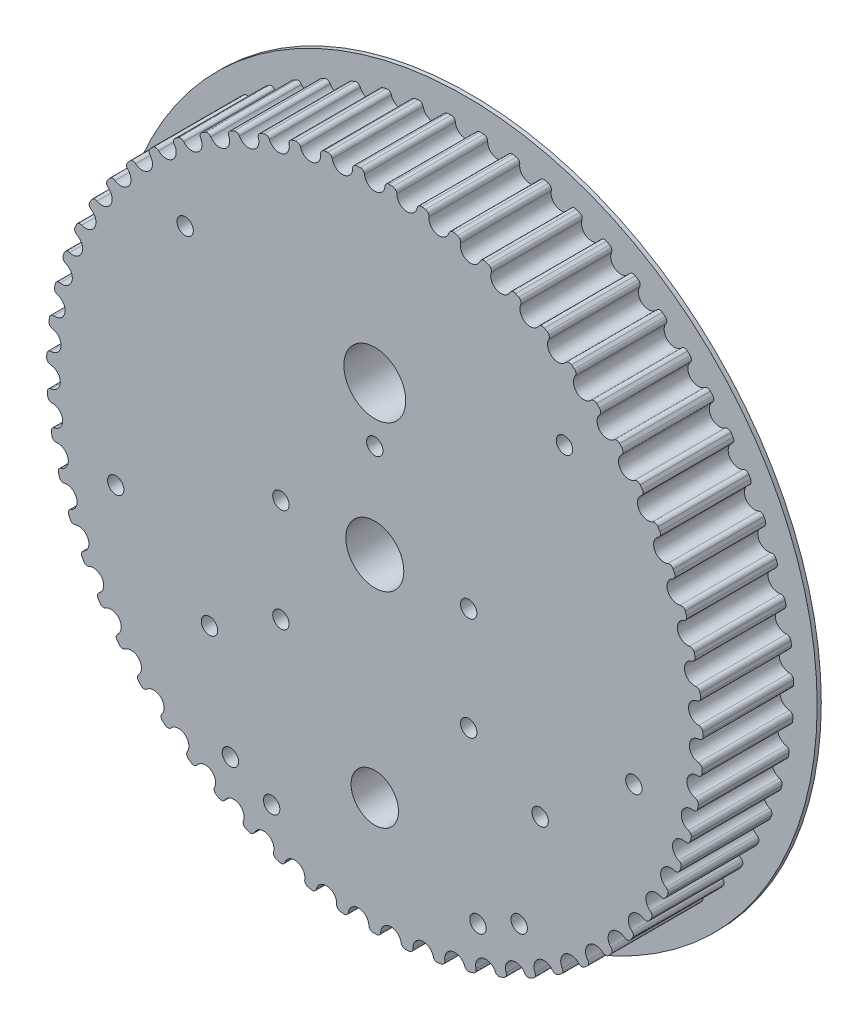
SolidWorks part; units mm, degrees
material "PETG"
ref_plane "Front Plane" through (0, 0, 0) normal (0, 0, 1) x (1, 0, 0)
ref_plane "Top Plane" through (0, 0, 0) normal (0, 1, 0) x (1, 0, 0)
ref_plane "Right Plane" through (0, 0, 0) normal (1, 0, 0) x (0, 0, -1)
sketch "Sketch1" plane through (0, 0, 0) normal (0, 0, 1) x (1, 0, 0)
  line L0 (0, 0) -> (0, 50000) construction
  line L1 (0, 0) -> (3.9983, 80.1144) construction
  line L2 (0, 0) -> (-3.9983, 80.1144) construction
  circle A0 centre (0, 0) radius 80.2141 construction
  arc A1 (-2.4816, 78.5352) -> (2.4816, 78.5352) centre (0, 78.74) ccw
  arc A2 (3.9642, 79.4311) -> (-3.9642, 79.4311) centre (0, 0) ccw construction
  arc A3 (-2.4816, 78.5352) -> (-3.5225, 79.452) centre (-3.4782, 78.4529) ccw
  arc A4 (3.5225, 79.452) -> (2.4816, 78.5352) centre (3.4782, 78.4529) ccw
  arc A5 (-3.5225, 79.452) -> (-3.9642, 79.4311) centre (0, 0) ccw
  arc A6 (3.5225, 79.452) -> (3.9642, 79.4311) centre (0, 0) cw
  arc A7 (4.4059, 79.4079) -> (3.9642, 79.4311) centre (0, 0) ccw
  arc A8 (5.3503, 78.392) -> (4.4059, 79.4079) centre (4.3505, 78.4094) ccw
  arc A9 (5.3503, 78.392) -> (10.2888, 77.8978) centre (7.84, 78.3487) ccw
  arc A10 (11.4158, 78.7064) -> (10.2888, 77.8978) centre (11.2723, 77.7168) ccw
  arc A11 (11.4158, 78.7064) -> (11.8533, 78.6417) centre (0, 0) cw
  arc A12 (12.2905, 78.5746) -> (11.8533, 78.6417) centre (0, 0) ccw
  arc A13 (13.1291, 77.4697) -> (12.2905, 78.5746) centre (12.1359, 77.5866) ccw
  arc A14 (13.1291, 77.4697) -> (17.9938, 76.4863) centre (15.602, 77.1788) ccw
  arc A15 (19.1957, 77.1787) -> (17.9938, 76.4863) centre (18.9544, 76.2082) ccw
  arc A16 (19.1957, 77.1787) -> (19.6246, 77.0707) centre (0, 0) cw
  arc A17 (20.0529, 76.9604) -> (19.6246, 77.0707) centre (0, 0) ccw
  arc A18 (20.7773, 75.7775) -> (20.0529, 76.9604) centre (19.8008, 75.9927) ccw
  arc A19 (20.7773, 75.7775) -> (25.52, 74.3146) centre (23.209, 75.2418) ccw
  arc A20 (26.7848, 74.8839) -> (25.52, 74.3146) centre (26.4481, 73.9423) ccw
  arc A21 (26.7848, 74.8839) -> (27.2009, 74.7338) centre (0, 0) cw
  arc A22 (27.616, 74.5813) -> (27.2009, 74.7338) centre (0, 0) ccw
  arc A23 (28.2191, 73.3322) -> (27.616, 74.5813) centre (27.2688, 73.6436) ccw
  arc A24 (28.2191, 73.3322) -> (32.7925, 71.4044) centre (30.5854, 72.557) ccw
  arc A25 (34.1078, 71.8448) -> (32.7925, 71.4044) centre (33.6789, 70.9415) ccw
  arc A26 (34.1078, 71.8448) -> (34.5068, 71.6541) centre (0, 0) cw
  arc A27 (34.9047, 71.4611) -> (34.5068, 71.6541) centre (0, 0) ccw
  arc A28 (35.3804, 70.1581) -> (34.9047, 71.4611) centre (34.4658, 70.5625) ccw
  arc A29 (35.3804, 70.1581) -> (39.7391, 67.7845) centre (37.6577, 69.1512) ccw
  arc A30 (41.0917, 68.0918) -> (39.7391, 67.7845) centre (40.575, 67.2356) ccw
  arc A31 (41.0917, 68.0918) -> (41.4697, 67.8622) centre (0, 0) cw
  arc A32 (41.8465, 67.6306) -> (41.4697, 67.8622) centre (0, 0) ccw
  arc A33 (42.1901, 66.2867) -> (41.8465, 67.6306) centre (41.3203, 66.7802) ccw
  arc A34 (42.1901, 66.2867) -> (46.2908, 63.4909) centre (44.3558, 65.058) ccw
  arc A35 (47.6673, 63.662) -> (46.2908, 63.4909) centre (47.0679, 62.8615) ccw
  arc A36 (47.6673, 63.662) -> (48.0206, 63.3959) centre (0, 0) cw
  arc A37 (48.3724, 63.1279) -> (48.0206, 63.3959) centre (0, 0) ccw
  arc A38 (48.5805, 61.7566) -> (48.3724, 63.1279) centre (47.7641, 62.3342) ccw
  arc A39 (48.5805, 61.7566) -> (52.3824, 58.5663) centre (50.6131, 60.3183) ccw
  arc A40 (53.7691, 58.5995) -> (52.3824, 58.5663) centre (53.093, 57.8627) ccw
  arc A41 (53.7691, 58.5995) -> (54.0941, 58.2996) centre (0, 0) cw
  arc A42 (54.4175, 57.9979) -> (54.0941, 58.2996) centre (0, 0) ccw
  arc A43 (54.488, 56.6126) -> (54.4175, 57.9979) centre (53.7333, 57.2686) ccw
  arc A44 (54.488, 56.6126) -> (57.9535, 53.0597) centre (56.3674, 54.9792) ccw
  arc A45 (59.3365, 52.9547) -> (57.9535, 53.0597) centre (58.5904, 52.2888) ccw
  arc A46 (59.3365, 52.9547) -> (59.6301, 52.6239) centre (0, 0) cw
  arc A47 (59.9218, 52.2915) -> (59.6301, 52.6239) centre (0, 0) ccw
  arc A48 (59.8541, 50.9061) -> (59.9218, 52.2915) centre (59.1684, 51.634) ccw
  arc A49 (59.8541, 50.9061) -> (62.9485, 47.0257) centre (61.5614, 49.0936) ccw
  arc A50 (64.3143, 46.7835) -> (62.9485, 47.0257) centre (63.5056, 46.1953) ccw
  arc A51 (64.3143, 46.7835) -> (64.5734, 46.4251) centre (0, 0) cw
  arc A52 (64.8306, 46.0653) -> (64.5734, 46.4251) centre (0, 0) ccw
  arc A53 (64.6252, 44.6936) -> (64.8306, 46.0653) centre (64.0154, 45.4861) ccw
  arc A54 (64.6252, 44.6936) -> (67.318, 40.5244) centre (66.1436, 42.7201) ccw
  arc A55 (68.6528, 40.1474) -> (67.318, 40.5244) centre (67.7896, 39.6426) ccw
  arc A56 (68.6528, 40.1474) -> (68.875, 39.765) centre (0, 0) cw
  arc A57 (69.0951, 39.3814) -> (68.875, 39.765) centre (0, 0) ccw
  arc A58 (68.7541, 38.0369) -> (69.0951, 39.3814) centre (68.2263, 38.8862) ccw
  arc A59 (68.7541, 38.0369) -> (71.0184, 33.6203) centre (70.0685, 35.922) ccw
  arc A60 (72.309, 33.1123) -> (71.0184, 33.6203) centre (71.3998, 32.6959) ccw
  arc A61 (72.309, 33.1123) -> (72.4921, 32.7097) centre (0, 0) cw
  arc A62 (72.6728, 32.306) -> (72.4921, 32.7097) centre (0, 0) ccw
  arc A63 (72.1997, 31.0021) -> (72.6728, 32.306) centre (71.7591, 31.8998) ccw
  arc A64 (72.1997, 31.0021) -> (74.013, 26.3821) centre (73.297, 28.767) ccw
  arc A65 (75.2466, 25.7481) -> (74.013, 26.3821) centre (74.3005, 25.4243) ccw
  arc A66 (75.2466, 25.7481) -> (75.3887, 25.3292) centre (0, 0) cw
  arc A67 (75.5284, 24.9096) -> (75.3887, 25.3292) centre (0, 0) ccw
  arc A68 (74.9278, 23.6593) -> (75.5284, 24.9096) centre (74.5787, 24.5964) ccw
  arc A69 (74.9278, 23.6593) -> (76.272, 18.8817) centre (75.797, 21.326) ccw
  arc A70 (77.4364, 18.128) -> (76.272, 18.8817) centre (76.4627, 17.9001) ccw
  arc A71 (77.4364, 18.128) -> (77.536, 17.6971) centre (0, 0) cw
  arc A72 (77.6332, 17.2656) -> (77.536, 17.6971) centre (0, 0) ccw
  arc A73 (76.9111, 16.0814) -> (77.6332, 17.2656) centre (76.6571, 17.0485) ccw
  arc A74 (76.9111, 16.0814) -> (77.773, 11.1936) centre (77.5438, 13.6731) ccw
  arc A75 (78.8566, 10.3277) -> (77.773, 11.1936) centre (77.865, 10.1979) ccw
  arc A76 (78.8566, 10.3277) -> (78.9128, 9.8891) centre (0, 0) cw
  arc A77 (78.9666, 9.4501) -> (78.9128, 9.8891) centre (0, 0) ccw
  arc A78 (78.1301, 8.3436) -> (78.9666, 9.4501) centre (77.9736, 9.3312) ccw
  arc A79 (78.1301, 8.3436) -> (78.501, 3.3943) centre (78.5198, 5.8842) ccw
  arc A80 (79.493, 2.4248) -> (78.501, 3.3943) centre (78.4935, 2.3943) ccw
  arc A81 (79.493, 2.4248) -> (79.5053, 1.9827) centre (0, 0) cw
  arc A82 (79.5151, 1.5406) -> (79.5053, 1.9827) centre (0, 0) ccw
  arc A83 (78.5726, 0.5229) -> (79.5151, 1.5406) centre (78.5153, 1.5212) ccw
  arc A84 (78.5726, 0.5229) -> (78.4489, -4.4387) centre (78.7155, -1.963) ccw
  arc A85 (79.3394, -5.5022) -> (78.4489, -4.4387) centre (78.3418, -5.433) ccw
  arc A86 (79.3394, -5.5022) -> (79.3076, -5.9433) centre (0, 0) cw
  arc A87 (79.2733, -6.3842) -> (79.3076, -5.9433) centre (0, 0) ccw
  arc A88 (78.2343, -7.3031) -> (79.2733, -6.3842) centre (78.2766, -6.3039) ccw
  arc A89 (78.2343, -7.3031) -> (77.6171, -12.2277) centre (78.1289, -9.7908) ccw
  arc A90 (78.3973, -13.3745) -> (77.6171, -12.2277) centre (77.4116, -13.2063) ccw
  arc A91 (78.3973, -13.3745) -> (78.3218, -13.8102) centre (0, 0) cw
  arc A92 (78.2438, -14.2456) -> (78.3218, -13.8102) centre (0, 0) ccw
  arc A93 (77.1183, -15.0564) -> (78.2438, -14.2456) centre (77.2599, -14.0665) ccw
  arc A94 (77.1183, -15.0564) -> (76.0139, -19.8951) centre (76.7658, -17.5213) ccw
  arc A95 (76.6761, -21.1139) -> (76.0139, -19.8951) centre (75.712, -20.8484) ccw
  arc A96 (76.6761, -21.1139) -> (76.5575, -21.5399) centre (0, 0) cw
  arc A97 (76.4365, -21.9653) -> (76.5575, -21.5399) centre (0, 0) ccw
  arc A98 (75.236, -22.6601) -> (76.4365, -21.9653) centre (75.4754, -21.6892) ccw
  arc A99 (75.236, -22.6601) -> (73.6553, -27.3648) centre (74.6398, -25.0776) ccw
  arc A100 (74.1928, -28.6434) -> (73.6553, -27.3648) centre (73.2599, -28.2833) ccw
  arc A101 (74.1928, -28.6434) -> (74.0324, -29.0556) centre (0, 0) cw
  arc A102 (73.8697, -29.4668) -> (74.0324, -29.0556) centre (0, 0) ccw
  arc A103 (72.6059, -30.0386) -> (73.8697, -29.4668) centre (72.9408, -29.0963) ccw
  arc A104 (72.6059, -30.0386) -> (70.5647, -34.5625) centre (71.772, -32.3847) ccw
  arc A105 (70.9722, -35.8883) -> (70.5647, -34.5625) centre (70.0798, -35.4371) ccw
  arc A106 (70.9722, -35.8883) -> (70.7715, -36.2824) centre (0, 0) cw
  arc A107 (70.5686, -36.6754) -> (70.7715, -36.2824) centre (0, 0) ccw
  arc A108 (69.2543, -37.1185) -> (70.5686, -36.6754) centre (69.6813, -36.2143) ccw
  arc A109 (69.2543, -37.1185) -> (66.7727, -41.4167) centre (68.1908, -39.37) ccw
  arc A110 (67.0462, -42.7765) -> (66.7727, -41.4167) centre (66.2031, -42.2387) ccw
  arc A111 (67.0462, -42.7765) -> (66.8073, -43.1487) centre (0, 0) cw
  arc A112 (66.5663, -43.5196) -> (66.8073, -43.1487) centre (0, 0) ccw
  arc A113 (65.2143, -43.8295) -> (66.5663, -43.5196) centre (65.7293, -42.9723) ccw
  arc A114 (65.2143, -43.8295) -> (62.3171, -47.8593) centre (63.932, -45.964) ccw
  arc A115 (62.4538, -49.2396) -> (62.3171, -47.8593) centre (61.6686, -48.6205) ccw
  arc A116 (62.4538, -49.2396) -> (62.1791, -49.5861) centre (0, 0) cw
  arc A117 (61.9023, -49.9312) -> (62.1791, -49.5861) centre (0, 0) ccw
  arc A118 (60.5262, -50.105) -> (61.9023, -49.9312) centre (61.124, -49.3033) ccw
  arc A119 (60.5262, -50.105) -> (57.2422, -53.8263) centre (59.0378, -52.1011) ccw
  arc A120 (57.2408, -55.2133) -> (57.2422, -53.8263) centre (56.5211, -54.5191) ccw
  arc A121 (57.2408, -55.2133) -> (56.9329, -55.5308) centre (0, 0) cw
  arc A122 (56.6232, -55.8465) -> (56.9329, -55.5308) centre (0, 0) ccw
  arc A123 (55.2366, -55.8825) -> (56.6232, -55.8465) centre (55.9112, -55.1443) ccw
  arc A124 (55.2366, -55.8825) -> (51.5984, -59.2583) centre (53.5568, -57.7205) ccw
  arc A125 (51.4589, -60.6383) -> (51.5984, -59.2583) centre (50.8119, -59.8758) ccw
  arc A126 (51.4589, -60.6383) -> (51.1209, -60.9235) centre (0, 0) cw
  arc A127 (50.7813, -61.2069) -> (51.1209, -60.9235) centre (0, 0) ccw
  arc A128 (49.398, -61.1046) -> (50.7813, -61.2069) centre (50.1428, -60.4372) ccw
  arc A129 (49.398, -61.1046) -> (45.4418, -64.1013) centre (47.5436, -62.7662) ccw
  arc A130 (45.1656, -65.4606) -> (45.4418, -64.1013) centre (44.5977, -64.6375) ccw
  arc A131 (45.1656, -65.4606) -> (44.8008, -65.7108) centre (0, 0) cw
  arc A132 (44.4347, -65.9589) -> (44.8008, -65.7108) centre (0, 0) ccw
  arc A133 (43.0685, -65.7194) -> (44.4347, -65.9589) centre (43.876, -65.1295) ccw
  arc A134 (43.0685, -65.7194) -> (38.8335, -68.3073) centre (41.0578, -67.1881) ccw
  arc A135 (38.4234, -69.6324) -> (38.8335, -68.3073) centre (37.9402, -68.7568) ccw
  arc A136 (38.4234, -69.6324) -> (38.0355, -69.845) centre (0, 0) cw
  arc A137 (37.6465, -70.0554) -> (38.0355, -69.845) centre (0, 0) ccw
  arc A138 (36.311, -69.6811) -> (37.6465, -70.0554) centre (37.1732, -69.1745) ccw
  arc A139 (36.311, -69.6811) -> (31.8393, -71.8345) centre (34.164, -70.9423) ccw
  arc A140 (31.2993, -73.1121) -> (31.8393, -71.8345) centre (30.9057, -72.1928) ccw
  arc A141 (31.2993, -73.1121) -> (30.8922, -73.285) centre (0, 0) cw
  arc A142 (30.4842, -73.4557) -> (30.8922, -73.285) centre (0, 0) ccw
  arc A143 (29.1925, -72.9502) -> (30.4842, -73.4557) centre (30.1009, -72.532) ccw
  arc A144 (29.1925, -72.9502) -> (24.5287, -74.6477) centre (26.9307, -73.9914) ccw
  arc A145 (23.8641, -75.8652) -> (24.5287, -74.6477) centre (23.5641, -74.9113) ccw
  arc A146 (23.8641, -75.8652) -> (23.4419, -75.9967) centre (0, 0) cw
  arc A147 (23.0189, -76.1259) -> (23.4419, -75.9967) centre (0, 0) ccw
  arc A148 (21.784, -75.4943) -> (23.0189, -76.1259) centre (22.7295, -75.1687) ccw
  arc A149 (21.784, -75.4943) -> (16.9743, -76.719) centre (19.4297, -76.3051) ccw
  arc A150 (16.1918, -77.8643) -> (16.9743, -76.719) centre (15.9882, -76.8852) ccw
  arc A151 (16.1918, -77.8643) -> (15.7586, -77.9531) centre (0, 0) cw
  arc A152 (15.3248, -78.0395) -> (15.7586, -77.9531) centre (0, 0) ccw
  arc A153 (14.1589, -77.2882) -> (15.3248, -78.0395) centre (15.1321, -77.0583) ccw
  arc A154 (14.1589, -77.2882) -> (9.2512, -78.0279) centre (11.7356, -77.8605) ccw
  arc A155 (8.3586, -79.0895) -> (9.2512, -78.0279) centre (8.2535, -78.0951) ccw
  arc A156 (8.3586, -79.0895) -> (7.9186, -79.1348) centre (0, 0) cw
  arc A157 (7.4784, -79.1776) -> (7.9186, -79.1348) centre (0, 0) ccw
  arc A158 (6.3931, -78.3139) -> (7.4784, -79.1776) centre (7.3844, -78.182) ccw
  arc A159 (6.3931, -78.3139) -> (1.4362, -78.5613) centre (3.9249, -78.6421) ccw
  arc A160 (0.4423, -79.5288) -> (1.4362, -78.5613) centre (0.4367, -78.5288) ccw
  arc A161 (0.4423, -79.5288) -> (0, -79.53) centre (0, 0) cw
  arc A162 (-0.4423, -79.5288) -> (0, -79.53) centre (0, 0) ccw
  arc A163 (-1.4362, -78.5613) -> (-0.4423, -79.5288) centre (-0.4367, -78.5288) ccw
  arc A164 (-1.4362, -78.5613) -> (-6.3931, -78.3139) centre (-3.9249, -78.6421) ccw
  arc A165 (-7.4784, -79.1776) -> (-6.3931, -78.3139) centre (-7.3844, -78.182) ccw
  arc A166 (-7.4784, -79.1776) -> (-7.9186, -79.1348) centre (0, 0) cw
  arc A167 (-8.3586, -79.0895) -> (-7.9186, -79.1348) centre (0, 0) ccw
  arc A168 (-9.2512, -78.0279) -> (-8.3586, -79.0895) centre (-8.2535, -78.0951) ccw
  arc A169 (-9.2512, -78.0279) -> (-14.1589, -77.2882) centre (-11.7356, -77.8605) ccw
  arc A170 (-15.3248, -78.0395) -> (-14.1589, -77.2882) centre (-15.1321, -77.0583) ccw
  arc A171 (-15.3248, -78.0395) -> (-15.7586, -77.9531) centre (0, 0) cw
  arc A172 (-16.1918, -77.8643) -> (-15.7586, -77.9531) centre (0, 0) ccw
  arc A173 (-16.9743, -76.719) -> (-16.1918, -77.8643) centre (-15.9882, -76.8852) ccw
  arc A174 (-16.9743, -76.719) -> (-21.784, -75.4943) centre (-19.4297, -76.3051) ccw
  arc A175 (-23.0189, -76.1259) -> (-21.784, -75.4943) centre (-22.7295, -75.1687) ccw
  arc A176 (-23.0189, -76.1259) -> (-23.4419, -75.9967) centre (0, 0) cw
  arc A177 (-23.8641, -75.8652) -> (-23.4419, -75.9967) centre (0, 0) ccw
  arc A178 (-24.5287, -74.6477) -> (-23.8641, -75.8652) centre (-23.5641, -74.9113) ccw
  arc A179 (-24.5287, -74.6477) -> (-29.1925, -72.9502) centre (-26.9307, -73.9914) ccw
  arc A180 (-30.4842, -73.4557) -> (-29.1925, -72.9502) centre (-30.1009, -72.532) ccw
  arc A181 (-30.4842, -73.4557) -> (-30.8922, -73.285) centre (0, 0) cw
  arc A182 (-31.2993, -73.1121) -> (-30.8922, -73.285) centre (0, 0) ccw
  arc A183 (-31.8393, -71.8345) -> (-31.2993, -73.1121) centre (-30.9057, -72.1928) ccw
  arc A184 (-31.8393, -71.8345) -> (-36.311, -69.6811) centre (-34.164, -70.9423) ccw
  arc A185 (-37.6465, -70.0554) -> (-36.311, -69.6811) centre (-37.1732, -69.1745) ccw
  arc A186 (-37.6465, -70.0554) -> (-38.0355, -69.845) centre (0, 0) cw
  arc A187 (-38.4234, -69.6324) -> (-38.0355, -69.845) centre (0, 0) ccw
  arc A188 (-38.8335, -68.3073) -> (-38.4234, -69.6324) centre (-37.9402, -68.7568) ccw
  arc A189 (-38.8335, -68.3073) -> (-43.0685, -65.7194) centre (-41.0578, -67.1881) ccw
  arc A190 (-44.4347, -65.9589) -> (-43.0685, -65.7194) centre (-43.876, -65.1295) ccw
  arc A191 (-44.4347, -65.9589) -> (-44.8008, -65.7108) centre (0, 0) cw
  arc A192 (-45.1656, -65.4606) -> (-44.8008, -65.7108) centre (0, 0) ccw
  arc A193 (-45.4418, -64.1013) -> (-45.1656, -65.4606) centre (-44.5977, -64.6375) ccw
  arc A194 (-45.4418, -64.1013) -> (-49.398, -61.1046) centre (-47.5436, -62.7662) ccw
  arc A195 (-50.7813, -61.2069) -> (-49.398, -61.1046) centre (-50.1428, -60.4372) ccw
  arc A196 (-50.7813, -61.2069) -> (-51.1209, -60.9235) centre (0, 0) cw
  arc A197 (-51.4589, -60.6383) -> (-51.1209, -60.9235) centre (0, 0) ccw
  arc A198 (-51.5984, -59.2583) -> (-51.4589, -60.6383) centre (-50.8119, -59.8758) ccw
  arc A199 (-51.5984, -59.2583) -> (-55.2366, -55.8825) centre (-53.5568, -57.7205) ccw
  arc A200 (-56.6232, -55.8465) -> (-55.2366, -55.8825) centre (-55.9112, -55.1443) ccw
  arc A201 (-56.6232, -55.8465) -> (-56.9329, -55.5308) centre (0, 0) cw
  arc A202 (-57.2408, -55.2133) -> (-56.9329, -55.5308) centre (0, 0) ccw
  arc A203 (-57.2422, -53.8263) -> (-57.2408, -55.2133) centre (-56.5211, -54.5191) ccw
  arc A204 (-57.2422, -53.8263) -> (-60.5262, -50.105) centre (-59.0378, -52.1011) ccw
  arc A205 (-61.9023, -49.9312) -> (-60.5262, -50.105) centre (-61.124, -49.3033) ccw
  arc A206 (-61.9023, -49.9312) -> (-62.1791, -49.5861) centre (0, 0) cw
  arc A207 (-62.4538, -49.2396) -> (-62.1791, -49.5861) centre (0, 0) ccw
  arc A208 (-62.3171, -47.8593) -> (-62.4538, -49.2396) centre (-61.6686, -48.6205) ccw
  arc A209 (-62.3171, -47.8593) -> (-65.2143, -43.8295) centre (-63.932, -45.964) ccw
  arc A210 (-66.5663, -43.5196) -> (-65.2143, -43.8295) centre (-65.7293, -42.9723) ccw
  arc A211 (-66.5663, -43.5196) -> (-66.8073, -43.1487) centre (0, 0) cw
  arc A212 (-67.0462, -42.7765) -> (-66.8073, -43.1487) centre (0, 0) ccw
  arc A213 (-66.7727, -41.4167) -> (-67.0462, -42.7765) centre (-66.2031, -42.2387) ccw
  arc A214 (-66.7727, -41.4167) -> (-69.2543, -37.1185) centre (-68.1908, -39.37) ccw
  arc A215 (-70.5686, -36.6754) -> (-69.2543, -37.1185) centre (-69.6813, -36.2143) ccw
  arc A216 (-70.5686, -36.6754) -> (-70.7715, -36.2824) centre (0, 0) cw
  arc A217 (-70.9722, -35.8883) -> (-70.7715, -36.2824) centre (0, 0) ccw
  arc A218 (-70.5647, -34.5625) -> (-70.9722, -35.8883) centre (-70.0798, -35.4371) ccw
  arc A219 (-70.5647, -34.5625) -> (-72.6059, -30.0386) centre (-71.772, -32.3847) ccw
  arc A220 (-73.8697, -29.4668) -> (-72.6059, -30.0386) centre (-72.9408, -29.0963) ccw
  arc A221 (-73.8697, -29.4668) -> (-74.0324, -29.0556) centre (0, 0) cw
  arc A222 (-74.1928, -28.6434) -> (-74.0324, -29.0556) centre (0, 0) ccw
  arc A223 (-73.6553, -27.3648) -> (-74.1928, -28.6434) centre (-73.2599, -28.2833) ccw
  arc A224 (-73.6553, -27.3648) -> (-75.236, -22.6601) centre (-74.6398, -25.0776) ccw
  arc A225 (-76.4365, -21.9653) -> (-75.236, -22.6601) centre (-75.4754, -21.6892) ccw
  arc A226 (-76.4365, -21.9653) -> (-76.5575, -21.5399) centre (0, 0) cw
  arc A227 (-76.6761, -21.1139) -> (-76.5575, -21.5399) centre (0, 0) ccw
  arc A228 (-76.0139, -19.8951) -> (-76.6761, -21.1139) centre (-75.712, -20.8484) ccw
  arc A229 (-76.0139, -19.8951) -> (-77.1183, -15.0564) centre (-76.7658, -17.5213) ccw
  arc A230 (-78.2438, -14.2456) -> (-77.1183, -15.0564) centre (-77.2599, -14.0665) ccw
  arc A231 (-78.2438, -14.2456) -> (-78.3218, -13.8102) centre (0, 0) cw
  arc A232 (-78.3973, -13.3745) -> (-78.3218, -13.8102) centre (0, 0) ccw
  arc A233 (-77.6171, -12.2277) -> (-78.3973, -13.3745) centre (-77.4116, -13.2063) ccw
  arc A234 (-77.6171, -12.2277) -> (-78.2343, -7.3031) centre (-78.1289, -9.7908) ccw
  arc A235 (-79.2733, -6.3842) -> (-78.2343, -7.3031) centre (-78.2766, -6.3039) ccw
  arc A236 (-79.2733, -6.3842) -> (-79.3076, -5.9433) centre (0, 0) cw
  arc A237 (-79.3394, -5.5022) -> (-79.3076, -5.9433) centre (0, 0) ccw
  arc A238 (-78.4489, -4.4387) -> (-79.3394, -5.5022) centre (-78.3418, -5.433) ccw
  arc A239 (-78.4489, -4.4387) -> (-78.5726, 0.5229) centre (-78.7155, -1.963) ccw
  arc A240 (-79.5151, 1.5406) -> (-78.5726, 0.5229) centre (-78.5153, 1.5212) ccw
  arc A241 (-79.5151, 1.5406) -> (-79.5053, 1.9827) centre (0, 0) cw
  arc A242 (-79.493, 2.4248) -> (-79.5053, 1.9827) centre (0, 0) ccw
  arc A243 (-78.501, 3.3943) -> (-79.493, 2.4248) centre (-78.4935, 2.3943) ccw
  arc A244 (-78.501, 3.3943) -> (-78.1301, 8.3436) centre (-78.5198, 5.8842) ccw
  arc A245 (-78.9666, 9.4501) -> (-78.1301, 8.3436) centre (-77.9736, 9.3312) ccw
  arc A246 (-78.9666, 9.4501) -> (-78.9128, 9.8891) centre (0, 0) cw
  arc A247 (-78.8566, 10.3277) -> (-78.9128, 9.8891) centre (0, 0) ccw
  arc A248 (-77.773, 11.1936) -> (-78.8566, 10.3277) centre (-77.865, 10.1979) ccw
  arc A249 (-77.773, 11.1936) -> (-76.9111, 16.0814) centre (-77.5438, 13.6731) ccw
  arc A250 (-77.6332, 17.2656) -> (-76.9111, 16.0814) centre (-76.6571, 17.0485) ccw
  arc A251 (-77.6332, 17.2656) -> (-77.536, 17.6971) centre (0, 0) cw
  arc A252 (-77.4364, 18.128) -> (-77.536, 17.6971) centre (0, 0) ccw
  arc A253 (-76.272, 18.8817) -> (-77.4364, 18.128) centre (-76.4627, 17.9001) ccw
  arc A254 (-76.272, 18.8817) -> (-74.9278, 23.6593) centre (-75.797, 21.326) ccw
  arc A255 (-75.5284, 24.9096) -> (-74.9278, 23.6593) centre (-74.5787, 24.5964) ccw
  arc A256 (-75.5284, 24.9096) -> (-75.3887, 25.3292) centre (0, 0) cw
  arc A257 (-75.2466, 25.7481) -> (-75.3887, 25.3292) centre (0, 0) ccw
  arc A258 (-74.013, 26.3821) -> (-75.2466, 25.7481) centre (-74.3005, 25.4243) ccw
  arc A259 (-74.013, 26.3821) -> (-72.1997, 31.0021) centre (-73.297, 28.767) ccw
  arc A260 (-72.6728, 32.306) -> (-72.1997, 31.0021) centre (-71.7591, 31.8998) ccw
  arc A261 (-72.6728, 32.306) -> (-72.4921, 32.7097) centre (0, 0) cw
  arc A262 (-72.309, 33.1123) -> (-72.4921, 32.7097) centre (0, 0) ccw
  arc A263 (-71.0184, 33.6203) -> (-72.309, 33.1123) centre (-71.3998, 32.6959) ccw
  arc A264 (-71.0184, 33.6203) -> (-68.7541, 38.0369) centre (-70.0685, 35.922) ccw
  arc A265 (-69.0951, 39.3814) -> (-68.7541, 38.0369) centre (-68.2263, 38.8862) ccw
  arc A266 (-69.0951, 39.3814) -> (-68.875, 39.765) centre (0, 0) cw
  arc A267 (-68.6528, 40.1474) -> (-68.875, 39.765) centre (0, 0) ccw
  arc A268 (-67.318, 40.5244) -> (-68.6528, 40.1474) centre (-67.7896, 39.6426) ccw
  arc A269 (-67.318, 40.5244) -> (-64.6252, 44.6936) centre (-66.1436, 42.7201) ccw
  arc A270 (-64.8306, 46.0653) -> (-64.6252, 44.6936) centre (-64.0154, 45.4861) ccw
  arc A271 (-64.8306, 46.0653) -> (-64.5734, 46.4251) centre (0, 0) cw
  arc A272 (-64.3143, 46.7835) -> (-64.5734, 46.4251) centre (0, 0) ccw
  arc A273 (-62.9485, 47.0257) -> (-64.3143, 46.7835) centre (-63.5056, 46.1953) ccw
  arc A274 (-62.9485, 47.0257) -> (-59.8541, 50.9061) centre (-61.5614, 49.0936) ccw
  arc A275 (-59.9218, 52.2915) -> (-59.8541, 50.9061) centre (-59.1684, 51.634) ccw
  arc A276 (-59.9218, 52.2915) -> (-59.6301, 52.6239) centre (0, 0) cw
  arc A277 (-59.3365, 52.9547) -> (-59.6301, 52.6239) centre (0, 0) ccw
  arc A278 (-57.9535, 53.0597) -> (-59.3365, 52.9547) centre (-58.5904, 52.2888) ccw
  arc A279 (-57.9535, 53.0597) -> (-54.488, 56.6126) centre (-56.3674, 54.9792) ccw
  arc A280 (-54.4175, 57.9979) -> (-54.488, 56.6126) centre (-53.7333, 57.2686) ccw
  arc A281 (-54.4175, 57.9979) -> (-54.0941, 58.2996) centre (0, 0) cw
  arc A282 (-53.7691, 58.5995) -> (-54.0941, 58.2996) centre (0, 0) ccw
  arc A283 (-52.3824, 58.5663) -> (-53.7691, 58.5995) centre (-53.093, 57.8627) ccw
  arc A284 (-52.3824, 58.5663) -> (-48.5805, 61.7566) centre (-50.6131, 60.3183) ccw
  arc A285 (-48.3724, 63.1279) -> (-48.5805, 61.7566) centre (-47.7641, 62.3342) ccw
  arc A286 (-48.3724, 63.1279) -> (-48.0206, 63.3959) centre (0, 0) cw
  arc A287 (-47.6673, 63.662) -> (-48.0206, 63.3959) centre (0, 0) ccw
  arc A288 (-46.2908, 63.4909) -> (-47.6673, 63.662) centre (-47.0679, 62.8615) ccw
  arc A289 (-46.2908, 63.4909) -> (-42.1901, 66.2867) centre (-44.3558, 65.058) ccw
  arc A290 (-41.8465, 67.6306) -> (-42.1901, 66.2867) centre (-41.3203, 66.7802) ccw
  arc A291 (-41.8465, 67.6306) -> (-41.4697, 67.8622) centre (0, 0) cw
  arc A292 (-41.0917, 68.0918) -> (-41.4697, 67.8622) centre (0, 0) ccw
  arc A293 (-39.7391, 67.7845) -> (-41.0917, 68.0918) centre (-40.575, 67.2356) ccw
  arc A294 (-39.7391, 67.7845) -> (-35.3804, 70.1581) centre (-37.6577, 69.1512) ccw
  arc A295 (-34.9047, 71.4611) -> (-35.3804, 70.1581) centre (-34.4658, 70.5625) ccw
  arc A296 (-34.9047, 71.4611) -> (-34.5068, 71.6541) centre (0, 0) cw
  arc A297 (-34.1078, 71.8448) -> (-34.5068, 71.6541) centre (0, 0) ccw
  arc A298 (-32.7925, 71.4044) -> (-34.1078, 71.8448) centre (-33.6789, 70.9415) ccw
  arc A299 (-32.7925, 71.4044) -> (-28.2191, 73.3322) centre (-30.5854, 72.557) ccw
  arc A300 (-27.616, 74.5813) -> (-28.2191, 73.3322) centre (-27.2688, 73.6436) ccw
  arc A301 (-27.616, 74.5813) -> (-27.2009, 74.7338) centre (0, 0) cw
  arc A302 (-26.7848, 74.8839) -> (-27.2009, 74.7338) centre (0, 0) ccw
  arc A303 (-25.52, 74.3146) -> (-26.7848, 74.8839) centre (-26.4481, 73.9423) ccw
  arc A304 (-25.52, 74.3146) -> (-20.7773, 75.7775) centre (-23.209, 75.2418) ccw
  arc A305 (-20.0529, 76.9604) -> (-20.7773, 75.7775) centre (-19.8008, 75.9927) ccw
  arc A306 (-20.0529, 76.9604) -> (-19.6246, 77.0707) centre (0, 0) cw
  arc A307 (-19.1957, 77.1787) -> (-19.6246, 77.0707) centre (0, 0) ccw
  arc A308 (-17.9938, 76.4863) -> (-19.1957, 77.1787) centre (-18.9544, 76.2082) ccw
  arc A309 (-17.9938, 76.4863) -> (-13.1291, 77.4697) centre (-15.602, 77.1788) ccw
  arc A310 (-12.2905, 78.5746) -> (-13.1291, 77.4697) centre (-12.1359, 77.5866) ccw
  arc A311 (-12.2905, 78.5746) -> (-11.8533, 78.6417) centre (0, 0) cw
  arc A312 (-11.4158, 78.7064) -> (-11.8533, 78.6417) centre (0, 0) ccw
  arc A313 (-10.2888, 77.8978) -> (-11.4158, 78.7064) centre (-11.2723, 77.7168) ccw
  arc A314 (-10.2888, 77.8978) -> (-5.3503, 78.392) centre (-7.84, 78.3487) ccw
  arc A315 (-4.4059, 79.4079) -> (-5.3503, 78.392) centre (-4.3505, 78.4094) ccw
  arc A316 (-4.4059, 79.4079) -> (-3.9642, 79.4311) centre (0, 0) cw
  point P0 (2.4816, 78.4529)
  point P9 (0, 76.25)
  point P11 (0, 80.2141)
  point P12 (0, 79.53)
  dimension "D1" = 160.4282
  dimension "D6" = 1
  dimension "D3" = 2.49
  dimension "D4" = 79.53
  dimension "D5" = 3.28
  dimension "D2" = 8
  dimension "D7" = 63
extrude "Boss-Extrude1" add sketch "Sketch1" along normal blind 22 contours A316 A315 A314 A313 A312 A311 A310 A309 A308 A307 A306 A305 A304 A303 A302 A301 A300 A299 A298 A297 A296 A295 A294 A293 A292 A291 A290 A289 A288 A287 A286 A285 A284 A283 A282 A281 A280 A279 A278 A277 A276 A275 A274 A273 A272 A271 A270 A269 A268 A267 A266 region at (0, 0, 0)
sketch "Sketch2" plane through (0, 0, 0) normal (0, 0, -1) x (-1, 0, 0)
  circle A0 centre (0, 0) radius 85.2141
  dimension "D1" = 170.4282
extrude "Boss-Extrude2" add sketch "Sketch2" along normal blind 1
sketch "Sketch3" plane through (0, 0, 22) normal (0, 0, 1) x (1, 0, 0)
  circle A0 centre (0, 0) radius 7.025
  circle A1 centre (0, -51.05) radius 5.75
  circle A2 centre (0, 36) radius 7.5
  dimension "D1" = 14.05
  dimension "D2" = 15
  dimension "D4" = 11.5
  dimension "D3" = 36
  dimension "D5" = 51.05
extrude "Cut-Extrude1" cut sketch "Sketch3" against normal through all
sketch "Sketch4" plane through (0, 0, 22) normal (0, 0, 1) x (1, 0, 0)
  line L0 (0, 0) -> (0, 50000) construction
  line L1 (0, 0) -> (-45.9619, 45.9619) construction
  line L2 (0, 0) -> (45.9619, 45.9619) construction
  line L3 (0, 0) -> (-62.7852, -16.8232) construction
  line L4 (0, 0) -> (62.7852, -16.8232) construction
  line L5 (-22.75, -25) -> (-40.0705, -35) construction
  line L6 (22.75, -25) -> (40.0705, -35) construction
  circle A0 centre (-45.9619, 45.9619) radius 1.985
  circle A1 centre (45.9619, 45.9619) radius 1.985
  circle A2 centre (-25, -65) radius 1.985
  circle A3 centre (25, -65) radius 1.985
  circle A4 centre (-62.7852, -16.8232) radius 1.985
  circle A5 centre (62.7852, -16.8232) radius 1.985
  circle A6 centre (-35, -60) radius 1.985
  circle A7 centre (35, -60) radius 1.985
  circle A8 centre (-22.75, 0) radius 1.985
  circle A9 centre (22.75, 0) radius 1.985
  circle A10 centre (0, 22.75) radius 1.985
  circle A11 centre (-22.75, -25) radius 1.985
  circle A12 centre (22.75, -25) radius 1.985
  circle A13 centre (-40.0705, -35) radius 1.985
  circle A14 centre (40.0705, -35) radius 1.985
  dimension "D1" = 3.97
  dimension "D2" = 65
  dimension "D3" = 45
  dimension "D4" = 25
  dimension "D5" = 65
  dimension "D6" = 25
  dimension "D7" = 60
  dimension "D8" = 35
  dimension "D9" = 60
  dimension "D10" = 35
  dimension "D11" = 22.75
  dimension "D12" = 22.75
  dimension "D13" = 22.75
  dimension "D14" = 25
  dimension "D15" = 60
  dimension "D16" = 20
extrude "Cut-Extrude2" cut sketch "Sketch4" against normal blind 18
equation "\"tol_dia_id_intfc\" = 0.0200mm ' For hole diameters - Interference fit"
equation "\"tol_dia_id_slip\"  = 0.0300mm ' For hole diameters - Slip fit"
equation "\"tol_dia_id_clear\" = 0.0500mm ' For hole diameters - Clearance fit"
equation "\"tol_dia_od_intfc\" = 0.0200mm ' For shaft diameters - Interference fit"
equation "\"tol_dia_od_slip\"  = 0.0300mm ' For shaft diameters - Slip fit"
equation "\"tol_dia_od_clear\" = 0.0500mm ' For shaft diameters - Clearance fit"
equation "\"tol_general_intfc\"= 0.0030mm ' For general parts (Horiz) - Interference fit"
equation "\"tol_general_slip\" = 0.0050mm ' For general parts (Horiz) - Slip fit"
equation "\"tol_general_clear\"= 0.0100mm ' For general parts (Horiz) - Clearance fit"
equation "\"tol_layer_intfc\"  = 0.0030mm ' For all parts (Vert) - Interference fit"
equation "\"tol_layer_slip\"   = 0.0050mm ' For all parts (Vert) - Slip fit"
equation "\"tol_layer_clear\"  = 0.0100mm ' For all parts (Vert) - Clearance fit"
equation "\"tol_corner_rad\"   = 0.100mm ' For corners that fit into other parts"
equation "\"pitch\"= 8mm"
equation "\"n\"= 63"
equation "\"pitch_dia\"= \"pitch\" * \"n\" / PI"
equation "\"belt_width\"= 22mm"
equation "\"D1@Sketch1\"=\"pitch_dia\""
equation "\"D2@Sketch1\"=\"pitch\""
equation "\"D7@Sketch1\"=\"n\""
equation "\"D1@Extrude-Thin2\"=\"belt_width\""
equation "\"D1@Boss-Extrude1\"=\"belt_width\""
equation "\"D1@Sketch2\"=\"pitch_dia\"+10"
equation "\"D1@Sketch3\"=14.00mm + \"tol_dia_id_clear\""
equation "\"D1@Sketch4\"=3.95+\"tol_dia_id_intfc\""
equation "\"D6@Sketch4\"=\"D4@Sketch4\""
equation "\"D10@Sketch4\"=\"D8@Sketch4\""
equation "\"D12@Sketch4\"=\"D11@Sketch4\""
equation "\"D13@Sketch4\"=\"D11@Sketch4\""
equation "\"outside_dia\"=159.06"
equation "\"D4@Sketch1\"=\"outside_dia\"/2"
